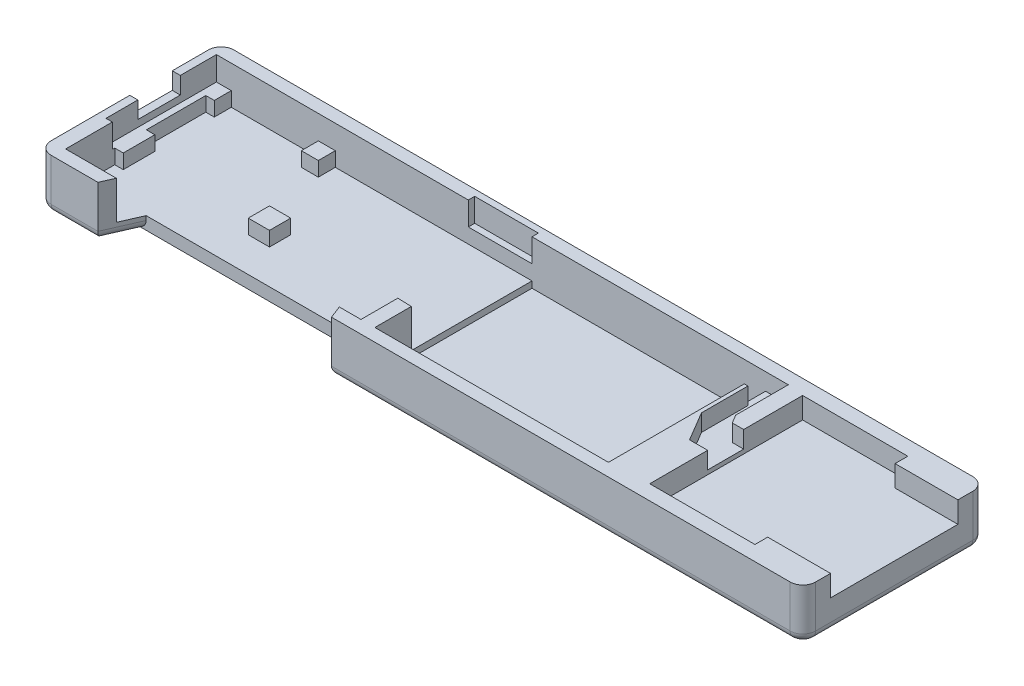
SolidWorks part; units mm, degrees
ref_plane "前视基准面" through (0, 0, 0) normal (0, 0, 1) x (1, 0, 0)
ref_plane "上视基准面" through (0, 0, 0) normal (0, 1, 0) x (1, 0, 0)
ref_plane "右视基准面" through (0, 0, 0) normal (1, 0, 0) x (0, 0, -1)
sketch "草图3" plane through (0, 0, 0) normal (0, 1, 0) x (1, 0, 0)
  line L1 (-39.9314, 29.2531) -> (140.0686, 29.2531)
  line L2 (-39.9314, 29.2531) -> (-39.9314, -13.7469)
  line L3 (-39.9314, -13.7469) -> (140.0686, -13.7469)
  line L4 (140.0686, 29.2531) -> (140.0686, -13.7469)
extrude "凸台-拉伸1" add sketch "草图3" along normal blind 12
sketch "草图4" plane through (0, 0, 0) normal (0, 1, 0) x (1, 0, 0)
  line L0 (-22.4696, -5.8589) -> (26.0023, -5.8589)
  line L1 (-39.9314, -13.7469) -> (140.0686, -13.7469) construction
  line L2 (-25.9314, -13.7469) -> (29.0686, -13.7469)
  line L5 (-25.9314, -13.7469) -> (-22.4696, -5.8589)
  line L6 (29.0686, -13.7469) -> (26.0023, -5.8589)
  point P11 (-22.4696, -5.8589)
  point P12 (26.0023, -5.8589)
extrude "切除-拉伸1" cut sketch "草图4" along normal blind 52
sketch "草图5" plane through (0, 12, 0) normal (0, 1, 0) x (1, 0, 0)
  line L6 (140.0686, -13.7469) -> (140.0686, 29.2531) construction
  line L7 (140.0686, 7.7531) -> (140.0686, 22.7531)
  line L8 (140.0686, 7.7531) -> (140.0686, -7.2469)
  line L9 (140.0686, 22.7531) -> (125.2765, 22.7531)
  line L10 (125.2765, 22.7531) -> (125.2765, -7.2469)
  line L11 (125.2765, -7.2469) -> (140.0686, -7.2469)
  point P0 (140.0686, 7.7531)
extrude "切除-拉伸2" cut sketch "草图5" against normal blind 5
sketch "草图7" plane through (0, 12, 0) normal (0, 1, 0) x (1, 0, 0)
  line L0 (125.2765, 22.7531) -> (125.2765, -7.2469) construction
  line L1 (125.2765, 7.7531) -> (125.2765, 25.7531)
  line L2 (125.2765, 7.7531) -> (125.2765, -10.2469)
  line L3 (125.2765, -10.2469) -> (100.5008, -10.2469)
  line L4 (100.5008, -10.2469) -> (100.5008, 25.7531)
  line L5 (100.5008, 25.7531) -> (125.2765, 25.7531)
  point P0 (125.2765, 7.7531)
extrude "切除-拉伸3" cut sketch "草图7" against normal blind 5
sketch "草图8" plane through (0, 12, 0) normal (0, 1, 0) x (1, 0, 0)
  line L1 (36.2763, 26.2531) -> (91.2763, 26.2531)
  line L2 (36.2763, 26.2531) -> (36.2763, -10.7469)
  line L3 (36.2763, -10.7469) -> (91.2763, -10.7469)
  line L4 (91.2763, 26.2531) -> (91.2763, -10.7469)
  line L6 (140.0686, 29.2531) -> (-39.9314, 29.2531) construction
  line L7 (29.0686, -13.7469) -> (140.0686, -13.7469) construction
  dimension "D1" = 3
  dimension "D2" = 3
extrude "切除-拉伸4" cut sketch "草图8" against normal blind 10.5
sketch "草图9" plane through (0, 12, 0) normal (0, 1, 0) x (1, 0, 0)
  line L0 (91.2763, -10.7469) -> (91.2763, 26.2531) construction
  line L1 (91.2763, 26.2531) -> (96.6358, 26.2531)
  line L2 (91.2763, 26.2531) -> (91.2763, 21.2551)
  line L4 (96.6358, 26.2531) -> (96.6358, 22.1306)
  line L5 (100.5008, 25.7531) -> (100.5008, -10.2469) construction
  line L7 (92.1327, 21.2551) -> (92.1327, 10.3104)
  line L12 (96.2367, 3.394) -> (100.5008, 3.394)
  line L13 (100.5008, 11.8772) -> (100.5008, 3.394)
  line L14 (92.1327, 10.3104) -> (96.2367, 3.394)
  line L15 (96.6358, 13.8621) -> (97.8136, 11.8772)
  line L17 (97.8136, 11.8772) -> (100.5008, 11.8772)
  line L19 (96.6358, 13.8621) -> (96.6358, 22.1306)
  line L20 (92.1327, 21.2551) -> (91.2763, 21.2551)
extrude "切除-拉伸5" cut sketch "草图9" against normal blind 4
sketch "草图10" plane through (0, 12, 0) normal (0, 1, 0) x (1, 0, 0)
  line L4 (-29.1302, -10.7469) -> (32.9986, -10.7469)
  line L5 (-29.1302, -10.7469) -> (-29.1302, -2.0631)
  line L6 (-29.1302, -2.0631) -> (32.9986, -2.0631)
  line L7 (32.9986, -10.7469) -> (32.9986, -2.0631)
extrude "切除-拉伸6" cut sketch "草图10" against normal blind 8
sketch "草图11" plane through (0, 12, 0) normal (0, 1, 0) x (1, 0, 0)
  line L0 (32.9986, -10.7469) -> (-36.5397, -10.7469)
  line L1 (36.2763, 26.2531) -> (36.2763, -10.7469) construction
  line L5 (-36.5397, 26.2531) -> (-36.5397, -10.7469)
  line L9 (36.2763, 26.2531) -> (36.2763, -2.1672)
  line L10 (-36.5397, 26.2531) -> (36.2763, 26.2531)
  line L11 (32.9986, -10.7469) -> (32.9986, -2.0631)
  line L12 (32.9986, -10.7469) -> (32.9986, -2.0631) construction
  line L13 (32.9986, -2.0631) -> (36.2763, -2.1672)
extrude "切除-拉伸8" cut sketch "草图11" against normal blind 9
fillet "圆角2" radius 2 7 edges at (140.0686, 0, -7.7531) (84.5686, 0, 13.7469) (27.5354, 0, 9.8029) (-24.2005, 0, 9.8029) (-32.9314, 0, 13.7469) (-39.9314, 0, -7.7531) (50.0686, 0, -29.2531)
fillet "圆角3" radius 3 8 edges at (-39.3456, 0.5858, -28.6673) (-39.3456, 0.5858, 13.1611) (139.4828, 0.5858, 13.1611) (139.4828, 0.5858, -28.6673) (140.0686, 7, -29.2531) (140.0686, 7, 13.7469) (-39.9314, 7, 13.7469) (-39.9314, 7, -29.2531)
sketch "草图12" plane through (-36.5397, 0, 0) normal (1, 0, 0) x (0, 0, -1)
  line L5 (7.7531, 12) -> (17.7531, 12)
  line L6 (7.7531, 12) -> (7.7531, 8)
  line L7 (7.7531, 8) -> (17.7531, 8)
  line L8 (17.7531, 12) -> (17.7531, 8)
  line L9 (26.2531, 3) -> (26.2531, 12) construction
  dimension "D1" = 10
  dimension "D2" = 8.5
  dimension "D3" = 4
extrude "切除-拉伸9" cut sketch "草图12" against normal blind 10
sketch "草图13" plane through (0, 3, 0) normal (0, 1, 0) x (1, 0, 0)
  line L0 (-36.5397, 26.2531) -> (-36.5397, -10.7469) construction
  line L1 (-36.5397, 22.2531) -> (-34.5397, 22.2531)
  line L2 (-36.5397, 22.2531) -> (-36.5397, 26.2531)
  line L3 (-36.5397, 26.2531) -> (-34.5397, 26.2531)
  line L4 (-34.5397, 22.2531) -> (-34.5397, 26.2531)
  line L5 (36.2763, 26.2531) -> (-36.5397, 26.2531) construction
  line L7 (-36.5397, 8.2531) -> (-34.5397, 8.2531)
  line L8 (-36.5397, 8.2531) -> (-36.5397, 0.8178)
  line L9 (-36.5397, 0.8178) -> (-34.5397, 0.8178)
  line L10 (-34.5397, 8.2531) -> (-34.5397, 0.8178)
  line L11 (-14.0397, 26.2531) -> (-10.0397, 26.2531)
  line L12 (-14.0397, 26.2531) -> (-14.0397, 22.2531)
  line L13 (-14.0397, 22.2531) -> (-10.0397, 22.2531)
  line L14 (-10.0397, 26.2531) -> (-10.0397, 22.2531)
  line L15 (-36.5397, 7.7531) -> (-36.5397, -10.7469) construction
  line L16 (-6.5397, 7.2531) -> (-1.5397, 7.2531)
  line L17 (-6.5397, 7.2531) -> (-6.5397, 2.2531)
  line L18 (-6.5397, 2.2531) -> (-1.5397, 2.2531)
  line L19 (-1.5397, 7.2531) -> (-1.5397, 2.2531)
  line L20 (96.6358, 26.2531) -> (-36.5397, 26.2531) construction
  point P16 (-14.0397, 24.2531)
  dimension "D1" = 14
  dimension "D2" = 4
  dimension "D3" = 2
  dimension "D4" = 2
  dimension "D5" = 22.5
  dimension "D6" = 4
  dimension "D7" = 4
  dimension "D8" = 30
  dimension "D9" = 5
  dimension "D10" = 5
  dimension "D11" = 19
extrude "凸台-拉伸2" add sketch "草图13" along normal blind 3.4
sketch "草图14" plane through (0, 12, 0) normal (0, 1, 0) x (1, 0, 0)
  line L0 (96.6358, 26.2531) -> (-36.5397, 26.2531) construction
  line L1 (36.2763, 26.2531) -> (21.2763, 26.2531)
  line L2 (36.2763, 26.2531) -> (36.2763, 27.7531)
  line L3 (36.2763, 27.7531) -> (21.2763, 27.7531)
  line L4 (21.2763, 26.2531) -> (21.2763, 27.7531)
  line L5 (91.2763, 26.2531) -> (36.2763, 26.2531) construction
  dimension "D1" = 15
extrude "切除-拉伸10" cut sketch "草图14" against normal blind 5.5
sketch "草图15" plane through (0, 12, 0) normal (0, 1, 0) x (1, 0, 0)
  line L6 (-36.5397, 0.2531) -> (-38.0397, 0.2531)
  line L7 (-36.5397, 0.2531) -> (-36.5397, 26.2531)
  line L8 (-36.5397, 26.2531) -> (-38.0397, 26.2531)
  line L9 (-38.0397, 0.2531) -> (-38.0397, 26.2531)
  point P5 (-36.5397, 26.2531)
  point P6 (0, 0)
  point P7 (-36.5397, 26.2531)
  dimension "D1" = 1.5
  dimension "D2" = 26
extrude "切除-拉伸11" cut sketch "草图15" against normal blind 5.6
equation "\"3。4.00mm\"=5"
